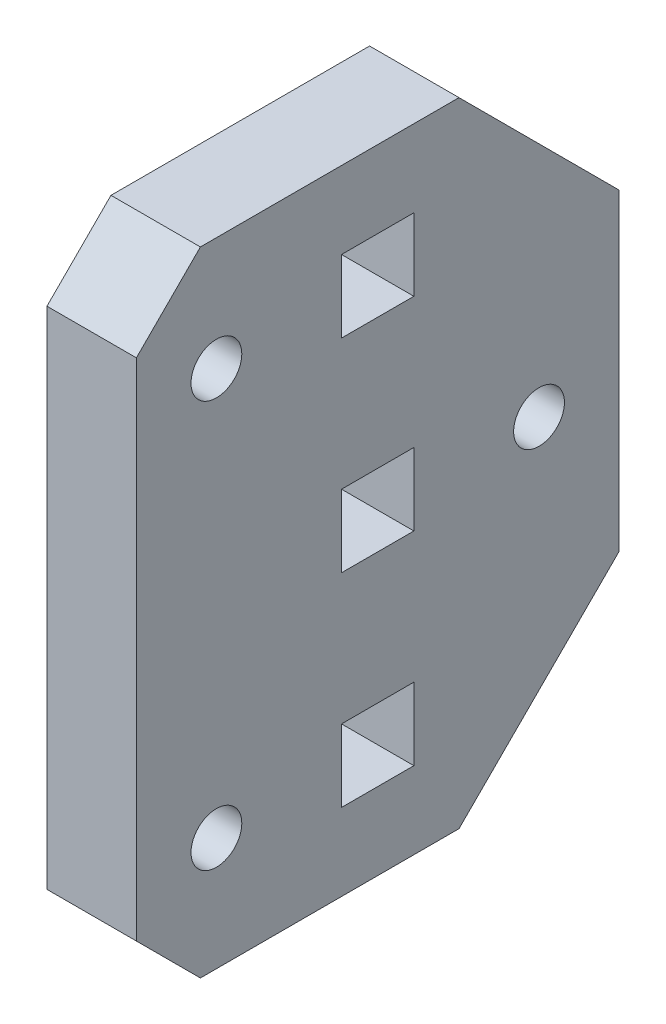
SolidWorks part; units mm, degrees
material "Beech"
ref_plane "Front" through (0, 0, 0) normal (0, 0, 1) x (1, 0, 0)
ref_plane "Top" through (0, 0, 0) normal (0, 1, 0) x (1, 0, 0)
ref_plane "Right" through (0, 0, 0) normal (1, 0, 0) x (0, 0, -1)
ref_axis "side-side" through (80.9, 0, 0) along (-1, 0, 0)
ref_axis "up-down" through (0, 50, 0) along (0, -1, 0)
ref_axis "front-back" through (0, 0, -80.9) along (0, 0, 1)
sketch "Sketch1" plane through (0, 0, 0) normal (1, 0, 0) x (0, 0, -1)
  line L0 (-2.2606, 14.9606) -> (2.2606, 10.4394) construction
  line L1 (-2.2606, 14.9606) -> (2.2606, 14.9606)
  line L2 (-2.2606, 14.9606) -> (-2.2606, 10.4394)
  line L3 (-2.2606, 10.4394) -> (2.2606, 10.4394)
  line L4 (2.2606, 14.9606) -> (2.2606, 10.4394)
  line L5 (-2.2606, 2.2606) -> (2.2606, -2.2606) construction
  line L6 (-2.2606, 2.2606) -> (2.2606, 2.2606)
  line L7 (-2.2606, 2.2606) -> (-2.2606, -2.2606)
  line L8 (-2.2606, -2.2606) -> (2.2606, -2.2606)
  line L9 (2.2606, 2.2606) -> (2.2606, -2.2606)
  line L10 (-2.2606, -10.4394) -> (2.2606, -10.4394)
  line L11 (-2.2606, -10.4394) -> (-2.2606, -14.9606)
  line L12 (-2.2606, -14.9606) -> (2.2606, -14.9606)
  line L13 (2.2606, -10.4394) -> (2.2606, -14.9606)
  line L14 (-2.2606, -10.4394) -> (2.2606, -14.9606) construction
  line L15 (-5.08, -15.2415) -> (-5.08, 15.2416) construction
  line L16 (-15.08, 19.78) -> (15.08, 19.78)
  line L17 (-15.08, 19.78) -> (-15.08, -19.78)
  line L18 (-15.08, -19.78) -> (15.08, -19.78)
  line L19 (15.08, 19.78) -> (15.08, -19.78)
  line L20 (5.08, 15.2416) -> (5.08, -15.2415) construction
  line L21 (-2.5415, 17.78) -> (2.5416, 17.78) construction
  line L22 (2.5416, -17.78) -> (-2.5415, -17.78) construction
  circle A0 centre (0, 12.7) radius 2.1209 construction
  circle A1 centre (0, -12.7) radius 2.1209 construction
  circle A2 centre (-10.08, 12.7) radius 1.5875
  circle A3 centre (-10.08, 12.7) radius 4.75 construction
  circle A4 centre (-10.08, -12.7) radius 1.5875
  circle A5 centre (10.08, 0) radius 1.5875
  point P6 (0, 12.7)
  point P17 (0, -12.7)
  dimension "D1" = 3.175
  dimension "D2" = 5
  dimension "D3" = 9.5
  dimension "D4" = 5
  dimension "D9" = 5
  dimension "D5" = 10.08
  dimension "D6" = 2
  dimension "D7" = 2
  dimension "D8" = 5
extrude "Boss-Extrude1" add sketch "Sketch1" along normal blind 5.588
chamfer "Chamfer1" distance 10 angle 45 2 edges at (2.794, -19.78, -15.08) (2.794, 19.78, -15.08)
chamfer "Chamfer2" distance 4 angle 45 2 edges at (2.794, 19.78, 15.08) (2.794, -19.78, 15.08)
